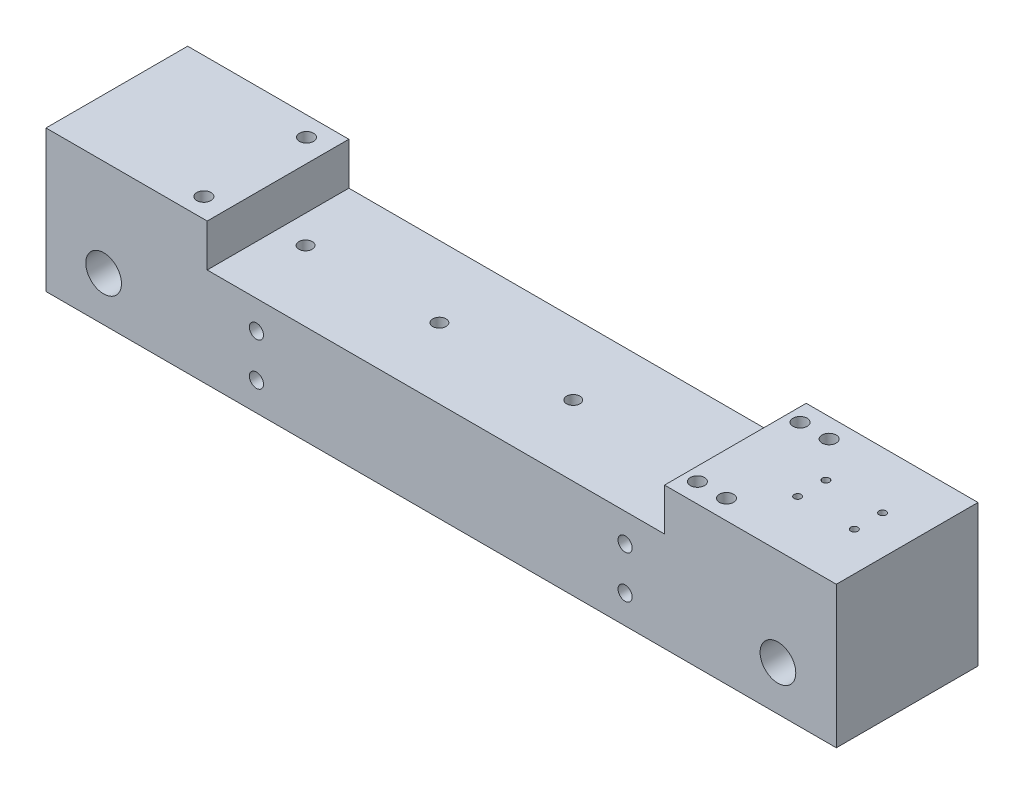
SolidWorks part; units mm, degrees
material "McMaster 6061-T6"
ref_plane "Front Plane" through (0, 0, 0) normal (0, 0, 1) x (1, 0, 0)
ref_plane "Top Plane" through (0, 0, 0) normal (0, 1, 0) x (1, 0, 0)
ref_plane "Right Plane" through (0, 0, 0) normal (1, 0, 0) x (0, 0, -1)
sketch "Sketch1" plane through (0, 0, 0) normal (0, 0, 1) x (1, 0, 0)
  line L0 (177.125, 59) -> (177.125, 63.5)
  line L1 (177.125, 63.5) -> (100.125, 63.5)
  line L2 (100.125, 63.5) -> (100.125, 59)
  line L3 (100.125, 44.5) -> (-104.875, 44.5)
  line L4 (-2.375, 44.5) -> (-2.375, 40)
  line L5 (-104.875, 63.5) -> (-177.125, 63.5)
  line L6 (-177.125, 63.5) -> (-177.125, 59)
  line L7 (-104.875, 63.5) -> (-104.875, 59)
  circle A0 centre (164.385, 33.435) radius 2.6035
  circle A1 centre (169.95, 20) radius 2.6035
  circle A2 centre (164.385, 6.565) radius 2.6035
  circle A3 centre (137.515, 6.565) radius 2.6035
  circle A4 centre (131.95, 20) radius 2.6035
  circle A5 centre (137.515, 33.435) radius 2.6035
  circle A6 centre (-137.865, 33.435) radius 2.6035
  circle A7 centre (-132.3, 20) radius 2.6035
  circle A8 centre (-137.865, 6.565) radius 2.6035
  circle A9 centre (-164.735, 6.565) radius 2.6035
  circle A10 centre (-170.3, 20) radius 2.6035
  circle A11 centre (-164.735, 33.435) radius 2.6035
  line B0 (-177.125, 0) -> (177.125, 0)
  line B1 (177.125, 0) -> (177.125, 59)
  line B2 (177.125, 59) -> (100.125, 59)
  line B3 (100.125, 59) -> (100.125, 40)
  line B4 (100.125, 40) -> (-104.875, 40)
  line B5 (-104.875, 40) -> (-104.875, 59)
  line B6 (-104.875, 59) -> (-177.125, 59)
  line B7 (-177.125, 59) -> (-177.125, 0)
  circle B8 centre (-151.3, 20) radius 14
  circle B9 centre (150.95, 20) radius 14
  arc B10 (-164.735, 9.315) -> (-164.735, 3.815) centre (-164.735, 6.565) ccw
  arc B11 (-164.735, 9.315) -> (-164.735, 3.815) centre (-164.735, 6.565) ccw
  arc B12 (-164.735, 3.815) -> (-164.735, 9.315) centre (-164.735, 6.565) ccw
  arc B13 (-164.735, 3.815) -> (-164.735, 9.315) centre (-164.735, 6.565) ccw
  arc B14 (-137.865, 3.815) -> (-137.865, 9.315) centre (-137.865, 6.565) ccw
  arc B15 (-137.865, 3.815) -> (-137.865, 9.315) centre (-137.865, 6.565) ccw
  arc B16 (-137.865, 9.315) -> (-137.865, 3.815) centre (-137.865, 6.565) ccw
  arc B17 (-137.865, 9.315) -> (-137.865, 3.815) centre (-137.865, 6.565) ccw
  arc B18 (-132.3, 17.25) -> (-132.3, 22.75) centre (-132.3, 20) ccw
  arc B19 (-132.3, 17.25) -> (-132.3, 22.75) centre (-132.3, 20) ccw
  arc B20 (-132.3, 22.75) -> (-132.3, 17.25) centre (-132.3, 20) ccw
  arc B21 (-132.3, 22.75) -> (-132.3, 17.25) centre (-132.3, 20) ccw
  arc B22 (-137.865, 30.685) -> (-137.865, 36.185) centre (-137.865, 33.435) ccw
  arc B23 (-137.865, 30.685) -> (-137.865, 36.185) centre (-137.865, 33.435) ccw
  arc B24 (-137.865, 36.185) -> (-137.865, 30.685) centre (-137.865, 33.435) ccw
  arc B25 (-137.865, 36.185) -> (-137.865, 30.685) centre (-137.865, 33.435) ccw
  arc B26 (-170.3, 17.25) -> (-170.3, 22.75) centre (-170.3, 20) ccw
  arc B27 (-170.3, 17.25) -> (-170.3, 22.75) centre (-170.3, 20) ccw
  arc B28 (-170.3, 22.75) -> (-170.3, 17.25) centre (-170.3, 20) ccw
  arc B29 (-170.3, 22.75) -> (-170.3, 17.25) centre (-170.3, 20) ccw
  arc B30 (-164.735, 30.685) -> (-164.735, 36.185) centre (-164.735, 33.435) ccw
  arc B31 (-164.735, 30.685) -> (-164.735, 36.185) centre (-164.735, 33.435) ccw
  arc B32 (-164.735, 36.185) -> (-164.735, 30.685) centre (-164.735, 33.435) ccw
  arc B33 (-164.735, 36.185) -> (-164.735, 30.685) centre (-164.735, 33.435) ccw
  arc B34 (137.515, 9.315) -> (137.515, 3.815) centre (137.515, 6.565) ccw
  arc B35 (137.515, 9.315) -> (137.515, 3.815) centre (137.515, 6.565) ccw
  arc B36 (137.515, 3.815) -> (137.515, 9.315) centre (137.515, 6.565) ccw
  arc B37 (137.515, 3.815) -> (137.515, 9.315) centre (137.515, 6.565) ccw
  arc B38 (164.385, 9.315) -> (164.385, 3.815) centre (164.385, 6.565) ccw
  arc B39 (164.385, 9.315) -> (164.385, 3.815) centre (164.385, 6.565) ccw
  arc B40 (164.385, 3.815) -> (164.385, 9.315) centre (164.385, 6.565) ccw
  arc B41 (164.385, 3.815) -> (164.385, 9.315) centre (164.385, 6.565) ccw
  arc B42 (169.95, 17.25) -> (169.95, 22.75) centre (169.95, 20) ccw
  arc B43 (169.95, 17.25) -> (169.95, 22.75) centre (169.95, 20) ccw
  arc B44 (169.95, 22.75) -> (169.95, 17.25) centre (169.95, 20) ccw
  arc B45 (169.95, 22.75) -> (169.95, 17.25) centre (169.95, 20) ccw
  arc B46 (164.385, 30.685) -> (164.385, 36.185) centre (164.385, 33.435) ccw
  arc B47 (164.385, 30.685) -> (164.385, 36.185) centre (164.385, 33.435) ccw
  arc B48 (164.385, 36.185) -> (164.385, 30.685) centre (164.385, 33.435) ccw
  arc B49 (164.385, 36.185) -> (164.385, 30.685) centre (164.385, 33.435) ccw
  arc B50 (131.95, 17.25) -> (131.95, 22.75) centre (131.95, 20) ccw
  arc B51 (131.95, 17.25) -> (131.95, 22.75) centre (131.95, 20) ccw
  arc B52 (131.95, 22.75) -> (131.95, 17.25) centre (131.95, 20) ccw
  arc B53 (131.95, 22.75) -> (131.95, 17.25) centre (131.95, 20) ccw
  arc B54 (137.515, 30.685) -> (137.515, 36.185) centre (137.515, 33.435) ccw
  arc B55 (137.515, 30.685) -> (137.515, 36.185) centre (137.515, 33.435) ccw
  arc B56 (137.515, 36.185) -> (137.515, 30.685) centre (137.515, 33.435) ccw
  arc B57 (137.515, 36.185) -> (137.515, 30.685) centre (137.515, 33.435) ccw
  dimension "D1" = 5.207
  dimension "D2" = 63.5
sketch_block_instance "Block-SecondaryBlock Sideview-1"
sketch_block "Block-SecondaryBlock Sideview"
extrude "Boss-Extrude1" add sketch "Sketch1" along normal blind 63.5 contours B6 B7 B0 B1 B2 B3 B4 B5 B56 B54 B52 B50 B48 B46 B44 B42 B40 B38 B36 B34 B32 B30 B28 B26 B24 B22 B20 B18 B16 B14 B12 B10 B9 B8 | B46 B48 A0 | B54 B56 A5 | B42 B44 A1 | B38 B40 A2 | B50 B52 A4 | B34 B36 A3 | B22 B24 A6 | B18 B20 A7 | B14 B16 A8 | B10 B12 A9 | B26 B28 A10 | B30 B32 A11 | B2 L0 L1 L2 | B4 B3 L3 L4 | B6 L7 L5 L6 | B5 B4 L4 L3 region at (138.625, 61.25, 0) region at (0.6144, 25.4009, 0) region at (48.875, 42.25, 0) region at (-141, 61.25, 0) region at (-53.625, 42.25, 0) region at (-162.0628, 6.565, 0) region at (-140.5372, 6.565, 0) region at (-134.9722, 20, 0) region at (-140.5372, 33.435, 0) region at (-172.9722, 20, 0) region at (-167.4072, 33.435, 0) region at (140.1872, 6.565, 0) region at (167.0572, 6.565, 0) region at (167.2778, 20, 0) region at (161.7128, 33.435, 0) region at (129.2778, 20, 0) region at (134.8428, 33.435, 0)
sketch "Sketch2" plane through (0, 63.5, 0) normal (0, 1, 0) x (1, 0, 0)
  line L0 (177.125, -61.75) -> (177.125, -1.75)
  line L2 (177.125, -63.5) -> (177.125, 0) construction
  circle A0 centre (119.125, -54.75) radius 3.175
  circle A1 centre (106.125, -54.75) radius 3.175
  circle A2 centre (119.125, -8.75) radius 3.175
  circle A3 centre (106.125, -8.75) radius 3.175
  circle A4 centre (-115.125, -54.75) radius 3.175
  circle A5 centre (-115.125, -8.75) radius 3.175
  point P13 (177.125, -31.75)
  point P20 (177.125, -31.75)
  line B0 (-177.125, -1.75) -> (177.125, -1.75)
  line B1 (177.125, -1.75) -> (177.125, -41.55)
  line B2 (177.125, -41.55) -> (-177.125, -41.55) construction
  line B3 (-177.125, -41.55) -> (-177.125, -1.75)
  line B4 (-177.125, -41.55) -> (-177.125, -61.75)
  line B5 (-177.125, -61.75) -> (177.125, -61.75)
  line B6 (177.125, -61.75) -> (177.125, -41.55)
  arc B7 (-118.425, -8.75) -> (-111.825, -8.75) centre (-115.125, -8.75) ccw
  arc B8 (-111.825, -8.75) -> (-118.425, -8.75) centre (-115.125, -8.75) ccw
  arc B9 (-118.425, -54.75) -> (-111.825, -54.75) centre (-115.125, -54.75) ccw
  arc B10 (-111.825, -54.75) -> (-118.425, -54.75) centre (-115.125, -54.75) ccw
  arc B11 (-132.725, -34.65) -> (-128.525, -34.65) centre (-130.625, -34.65) ccw
  arc B12 (-128.525, -34.65) -> (-132.725, -34.65) centre (-130.625, -34.65) ccw
  arc B13 (-132.725, -8.65) -> (-128.525, -8.65) centre (-130.625, -8.65) ccw
  arc B14 (-128.525, -8.65) -> (-132.725, -8.65) centre (-130.625, -8.65) ccw
  arc B15 (-173.725, -34.65) -> (-169.525, -34.65) centre (-171.625, -34.65) ccw
  arc B16 (-169.525, -34.65) -> (-173.725, -34.65) centre (-171.625, -34.65) ccw
  arc B17 (-173.725, -8.65) -> (-169.525, -8.65) centre (-171.625, -8.65) ccw
  arc B18 (-169.525, -8.65) -> (-173.725, -8.65) centre (-171.625, -8.65) ccw
  arc B19 (128.525, -8.65) -> (132.725, -8.65) centre (130.625, -8.65) ccw
  arc B20 (132.725, -8.65) -> (128.525, -8.65) centre (130.625, -8.65) ccw
  arc B21 (169.525, -8.65) -> (173.725, -8.65) centre (171.625, -8.65) ccw
  arc B22 (173.725, -8.65) -> (169.525, -8.65) centre (171.625, -8.65) ccw
  arc B23 (169.525, -34.65) -> (173.725, -34.65) centre (171.625, -34.65) ccw
  arc B24 (173.725, -34.65) -> (169.525, -34.65) centre (171.625, -34.65) ccw
  arc B25 (128.525, -34.65) -> (132.725, -34.65) centre (130.625, -34.65) ccw
  arc B26 (132.725, -34.65) -> (128.525, -34.65) centre (130.625, -34.65) ccw
  arc B27 (115.825, -54.75) -> (122.425, -54.75) centre (119.125, -54.75) ccw
  arc B28 (122.425, -54.75) -> (115.825, -54.75) centre (119.125, -54.75) ccw
  arc B29 (102.825, -54.75) -> (109.425, -54.75) centre (106.125, -54.75) ccw
  arc B30 (109.425, -54.75) -> (102.825, -54.75) centre (106.125, -54.75) ccw
  arc B31 (115.825, -8.75) -> (122.425, -8.75) centre (119.125, -8.75) ccw
  arc B32 (122.425, -8.75) -> (115.825, -8.75) centre (119.125, -8.75) ccw
  arc B33 (102.825, -8.75) -> (109.425, -8.75) centre (106.125, -8.75) ccw
  arc B34 (109.425, -8.75) -> (102.825, -8.75) centre (106.125, -8.75) ccw
  dimension "D1" = 6.35
sketch_block_instance "Block-SecondaryBlock Topview-1"
sketch_block "Block-SecondaryBlock Topview"
extrude "Cut-Extrude1" cut sketch "Sketch2" against normal blind 19.05 contours A0 | A1 | A2 | A3 | A4 | A5 region at (119.125, 63.5, 54.75) region at (106.125, 63.5, 54.75) region at (119.125, 63.5, 8.75) region at (106.125, 63.5, 8.75) region at (-115.125, 63.5, 54.75) region at (-115.125, 63.5, 8.75)
extrude "Cut-Extrude3" cut sketch "Sketch2<3>" along normal blind 6.35 from surface contours B23 B24 | B25 B26 | B19 B20 | B21 B22 | B11 B12 | B13 B14 | B17 B18 | B15 B16 region at (-130.625, 63.5, 34.65) region at (-130.625, 63.5, 8.65) region at (-171.625, 63.5, 34.65) region at (-171.625, 63.5, 8.65) region at (130.625, 63.5, 8.65) region at (171.625, 63.5, 8.65) region at (171.625, 63.5, 34.65) region at (130.625, 63.5, 34.65) starting at face at (0, 0, 31.75)
sketch "Sketch2<3>" plane through (0, 63.5, 0) normal (0, 1, 0) x (1, 0, 0) same geometry as "Sketch2"
sketch "Sketch3" plane through (0, 0, 0) normal (0, 0, -1) x (-1, 0, 0)
  circle A1 centre (-150.95, 20) radius 8
  circle A3 centre (-150.95, 20) radius 14
  circle A4 centre (-150.95, 20) radius 14 construction
  circle A5 centre (151.3, 20) radius 8
  circle A6 centre (151.3, 20) radius 14
  circle A7 centre (151.3, 20) radius 14 construction
  dimension "D2" = 16
extrude "Boss-Extrude2" add sketch "Sketch3" along normal offset from surface (31.5 mm away) 32 from surface up to face at (164.95, 20, 0) starting at face at (164.95, 20, 63.5)
sketch "Sketch4" plane through (0, 63.5, 0) normal (0, 1, 0) x (1, 0, 0)
  line L0 (177.125, -63.5) -> (177.125, 0) construction
  point P1 (100.125, -31.75)
  point P5 (177.125, -31.75)
  line B0 (177.125, -1.75) -> (100.125, -1.75)
  line B1 (100.125, -1.75) -> (100.125, -61.75)
  line B2 (100.125, -61.75) -> (177.125, -61.75)
  line B3 (177.125, -61.75) -> (177.125, -1.75)
  line B4 (128.025, -22.25) -> (128.025, -41.25) construction
  line B5 (128.025, -22.25) -> (166.125, -22.25) construction
  line B6 (128.025, -41.25) -> (166.125, -41.25) construction
  line B7 (166.125, -22.25) -> (166.125, -41.25) construction
  circle B8 centre (134.375, -38.075) radius 1.5875
  circle B9 centre (134.375, -25.425) radius 1.5875
  circle B10 centre (159.775, -25.425) radius 1.5875
  circle B11 centre (159.775, -38.075) radius 1.5875
sketch_block_instance "Block-MotorMounting TopView 2-1"
sketch_block "Block-MotorMounting TopView 2"
extrude "Cut-Extrude4" cut sketch "Sketch4" against normal blind 6.35 contours B11 | B10 | B9 | B8 region at (134.375, 63.5, 38.075) region at (134.375, 63.5, 25.425) region at (159.775, 63.5, 25.425) region at (159.775, 63.5, 38.075)
sketch "Sketch5" plane through (0, 0, 63.5) normal (0, 0, 1) x (1, 0, 0)
  circle A0 centre (131.95, 20) radius 2.6035 construction
  circle A1 centre (137.515, 6.565) radius 2.6035 construction
  circle A2 centre (164.385, 6.565) radius 2.6035 construction
  circle A3 centre (169.95, 20) radius 2.6035 construction
  circle A4 centre (164.385, 33.435) radius 2.6035 construction
  circle A5 centre (137.515, 33.435) radius 2.6035 construction
  circle A6 centre (-137.865, 6.565) radius 2.6035 construction
  circle A7 centre (-132.3, 20) radius 2.6035 construction
  circle A8 centre (-137.865, 33.435) radius 2.6035 construction
  circle A9 centre (-164.735, 6.565) radius 2.6035 construction
  circle A10 centre (-170.3, 20) radius 2.6035 construction
  circle A11 centre (-164.735, 33.435) radius 2.6035 construction
  circle A12 centre (131.95, 20) radius 2.6035
  circle A13 centre (137.515, 6.565) radius 2.6035
  circle A14 centre (164.385, 6.565) radius 2.6035
  circle A15 centre (169.95, 20) radius 2.6035
  circle A16 centre (164.385, 33.435) radius 2.6035
  circle A17 centre (137.515, 33.435) radius 2.6035
  circle A18 centre (-137.865, 6.565) radius 2.6035
  circle A19 centre (-132.3, 20) radius 2.6035
  circle A20 centre (-137.865, 33.435) radius 2.6035
  circle A21 centre (-164.735, 6.565) radius 2.6035
  circle A22 centre (-170.3, 20) radius 2.6035
  circle A23 centre (-164.735, 33.435) radius 2.6035
extrude "Boss-Extrude3" add sketch "Sketch5" against normal offset from surface (50.8 mm away) 12.7 up to face at (164.95, 20, 0)
sketch "Sketch6" plane through (0, 44.5, 0) normal (0, 1, 0) x (1, 0, 0)
  line B0 (-104.875, -25.8312) -> (-104.875, -38.0188)
  line B1 (-104.875, -38.0188) -> (100.125, -38.0188)
  line B2 (100.125, -38.0188) -> (100.125, -25.8312)
  line B3 (100.125, -25.8312) -> (-104.875, -25.8312)
  line B4 (100.125, 0) -> (-104.875, 0)
  line B5 (-104.875, 0) -> (-104.875, -63.5)
  line B6 (-104.875, -63.5) -> (100.125, -63.5)
  line B7 (100.125, -63.5) -> (100.125, 0)
  arc B8 (27.625, -34.925) -> (27.625, -28.925) centre (27.625, -31.925) ccw
  arc B9 (27.625, -28.925) -> (27.625, -34.925) centre (27.625, -31.925) ccw
  arc B10 (87.625, -34.925) -> (87.625, -28.925) centre (87.625, -31.925) ccw
  arc B11 (87.625, -28.925) -> (87.625, -34.925) centre (87.625, -31.925) ccw
  arc B12 (-32.3698, -34.925) -> (-32.3698, -28.925) centre (-32.3698, -31.925) ccw
  arc B13 (-32.3698, -28.925) -> (-32.3698, -34.925) centre (-32.3698, -31.925) ccw
  arc B14 (-92.3646, -34.925) -> (-92.3646, -28.925) centre (-92.3646, -31.925) ccw
  arc B15 (-92.3646, -28.925) -> (-92.3646, -34.925) centre (-92.3646, -31.925) ccw
sketch_block_instance "Block-CarriageMountingTop-1"
sketch_block "Block-CarriageMountingTop" parameters "D1"=60
extrude "Cut-Extrude5" cut sketch "Sketch6" against normal blind 6.35 contours B10 B11 | B8 B9 | B12 B13 | B14 B15 region at (27.625, 44.5, 31.925) region at (87.625, 44.5, 31.925) region at (-32.3698, 44.5, 31.925) region at (-92.3646, 44.5, 31.925)
fillet "Fillet1" [suppressed] radius 1.27
sketch "Sketch7" plane through (0, 0, 63.5) normal (0, 0, 1) x (1, 0, 0)
  line B0 (-177.125, 0) -> (177.125, 0) construction
  circle B1 centre (-82.8012, 31.8013) radius 3.175
  circle B2 centre (-82.8012, 12.7513) radius 3.175
  circle B3 centre (82.4512, 12.7513) radius 3.175
  circle B4 centre (82.4512, 31.8013) radius 3.175
sketch_block_instance "Block-SensorMountingtoGantry-1"
sketch_block "Block-SensorMountingtoGantry"
extrude "Cut-Extrude6" cut sketch "Sketch7" against normal blind 6.35
